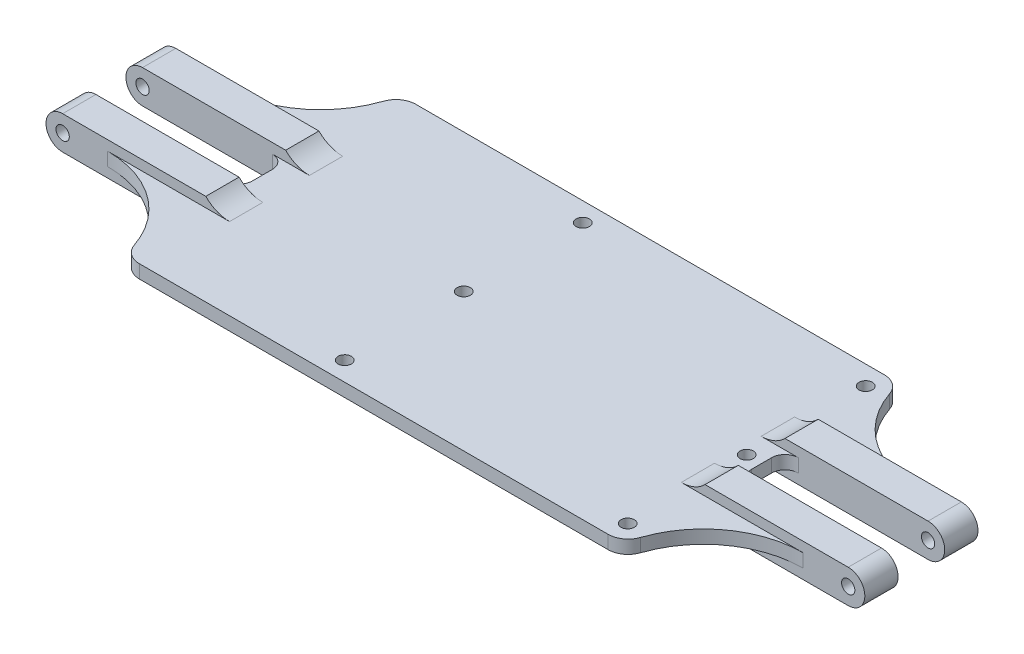
SolidWorks part; units mm, degrees
ref_plane "Front Plane" through (0, 0, 0) normal (0, 0, 1) x (1, 0, 0)
ref_plane "Top Plane" through (0, 0, 0) normal (0, 1, 0) x (1, 0, 0)
ref_plane "Right Plane" through (0, 0, 0) normal (1, 0, 0) x (0, 0, -1)
sketch "Sketch1" plane through (0, 0, 0) normal (0, 1, 0) x (1, 0, 0)
  line L0 (0, 121.3543) -> (0, -121.3543) construction
  line L1 (-75, -41.5) -> (75, -41.5)
  line L2 (-75, -41.5) -> (-75, 41.5)
  line L3 (-75, 41.5) -> (75, 41.5)
  line L4 (75, -41.5) -> (75, 41.5)
  line L5 (-75, -41.5) -> (75, 41.5) construction
  line L6 (-75, 41.5) -> (75, -41.5) construction
  line L7 (-246.33, 0) -> (246.33, 0) construction
  line L8 (-75, 7) -> (-124, 7)
  line L9 (-124, 7) -> (-124, 17)
  line L10 (-124, 17) -> (-75, 17)
  line L11 (-124, -17) -> (-75, -17)
  line L12 (-124, -7) -> (-124, -17)
  line L13 (-75, -7) -> (-124, -7)
  line L14 (-118, 46.0679) -> (-118, -44.6537) construction
  line L15 (124, -17) -> (75, -17)
  line L16 (124, -7) -> (124, -17)
  line L17 (75, -7) -> (124, -7)
  line L18 (75, 7) -> (124, 7)
  line L19 (124, 7) -> (124, 17)
  line L20 (124, 17) -> (75, 17)
  circle A0 centre (70.5, 35.75) radius 2
  circle A1 centre (70.5, 0) radius 2
  circle A2 centre (70.5, -35.75) radius 2
  circle A3 centre (-14.5, -35.75) radius 2
  circle A4 centre (-14.5, 0) radius 2
  circle A5 centre (-14.5, 35.75) radius 2
  point P0 (0, 0)
  point P8 (0, 0)
  point P11 (0, 0)
  dimension "D7" = 4
  dimension "D8" = 4
  dimension "D9" = 4
  dimension "D10" = 4
  dimension "D11" = 4
  dimension "D12" = 4
  dimension "D1" = 83
  dimension "D2" = 150
  dimension "D3" = 14
  dimension "D4" = 10
  dimension "D5" = 43
  dimension "D6" = 6
extrude "Boss-Extrude1" add sketch "Sketch1" along normal mid plane 10 contours L10 L9 L8 L2 | L2 L13 L12 L11 | L19 L20 L4 L18 | L17 L4 L15 L16 region at (-99.5, 0, 12) region at (99.5, 0, 12) region at (-99.5, 0, -12) region at (99.5, 0, -12)
sketch "Sketch2" plane through (0, 0, -17) normal (0, 0, -1) x (-1, 0, 0)
  line L0 (-124, -5) -> (-75, -5) construction
  line L1 (-124, 5) -> (-75, 5) construction
  line L2 (-124, 5) -> (-124, -5) construction
  line L6 (0, 69.849) -> (0, -80.9232) construction
  line L10 (-118, 5) -> (-118, 9.5057)
  line L11 (-118, 9.5057) -> (-152.7264, 9.5057)
  line L12 (-152.7264, 9.5057) -> (-152.7264, -6.9043)
  line L13 (-152.7264, -6.9043) -> (-118, -6.9043)
  line L14 (-118, -6.9043) -> (-118, -5)
  line L15 (118, 5) -> (118, 9.5057)
  line L16 (118, 9.5057) -> (152.7264, 9.5057)
  line L17 (152.7264, 9.5057) -> (152.7264, -6.9043)
  line L18 (152.7264, -6.9043) -> (118, -6.9043)
  line L19 (118, -6.9043) -> (118, -5)
  arc A0 (-118, -5) -> (-118, 5) centre (-118, 0) cw
  circle A1 centre (-118, 0) radius 2
  circle A2 centre (118, 0) radius 2
  arc A3 (118, -5) -> (118, 5) centre (118, 0) ccw
  dimension "D2" = 4
  dimension "D1" = 6
extrude "Cut-Extrude7" cut sketch "Sketch2" against normal through all both and the other way through all
extrude "Boss-Extrude2" add sketch "Sketch1<3>" along normal mid plane 4 contours L1 L4 L3 L2 region at (-0.1706, 0, 0)
sketch "Sketch1<3>" plane through (0, 0, 0) normal (0, 1, 0) x (1, 0, 0) same geometry as "Sketch1"
fillet "Fillet1" radius 10 4 edges at (-75, 2, -12) (-75, 2, 12) (75, 2, -12) (75, 2, 12)
sketch "Sketch3" plane through (0, -2, 0) normal (0, -1, 0) x (1, 0, 0)
  line L0 (-75, 17) -> (75, 17)
  line L1 (-75, 7) -> (75, 7)
  line L2 (-75, -7) -> (75, -7)
  line L3 (-75, -17) -> (75, -17)
  line L4 (-75, -17) -> (-75, -7)
  line L5 (75, -17) -> (75, -7)
  line L6 (75, 7) -> (75, 17)
  line L7 (-75, 7) -> (-75, 17)
extrude "Boss-Extrude3" add sketch "Sketch3" along normal up to surface (3 mm away) up to face at (96.5, -5, 13.25)
fillet "Fillet2" radius 30 4 edges at (-75, 0, 17) (-75, 0, -17) (75, 0, 17) (75, 0, -17)
fillet "Fillet3" radius 4 4 edges at (75, 0, 7) (75, 0, -7) (-75, 0, 7) (-75, 0, -7)
fillet "Fillet4" radius 6 4 edges at (75, 0, 41.5) (-75, 0, 41.5) (75, 0, -41.5) (-75, 0, -41.5)
